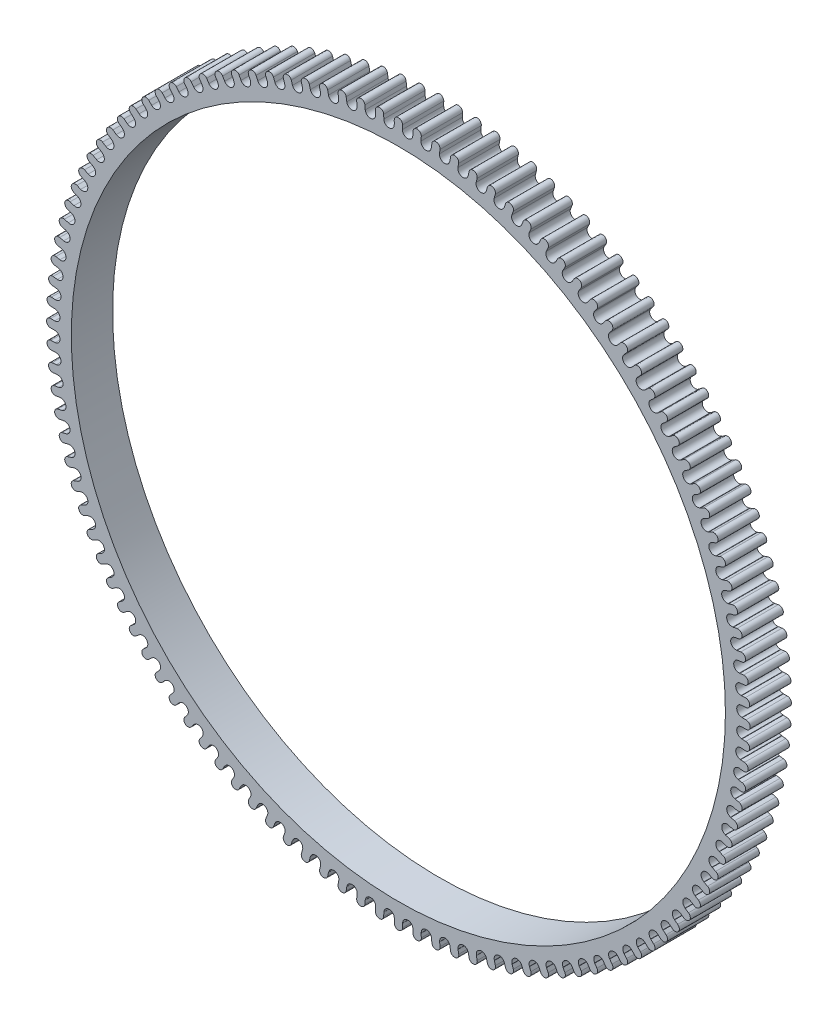
SolidWorks part; units mm, degrees
ref_plane "Front Plane" through (0, 0, 0) normal (0, 0, 1) x (1, 0, 0)
ref_plane "Top Plane" through (0, 0, 0) normal (0, 1, 0) x (1, 0, 0)
ref_plane "Right Plane" through (0, 0, 0) normal (1, 0, 0) x (0, 0, -1)
sketch "Sketch1" plane through (0, 0, 0) normal (0, 0, 1) x (1, 0, 0)
  circle A0 centre (0, 0) radius 79.25
  circle A1 centre (0, 0) radius 81.25
  dimension "D1" = 158.5
  dimension "D2" = 2
extrude "Boss-Extrude1" add sketch "Sketch1" along normal blind 10
sketch "Sketch2" plane through (0, 0, 10) normal (0, 0, 1) x (1, 0, 0)
  line L1 (1, 84.25) -> (0.9834, 83.25)
  line L2 (3.6329, 83.2298) -> (3.5431, 81.1727)
  line L3 (-1, 84.25) -> (-0.9643, 81.2443)
  line L4 (1, 84.25) -> (0.9997, 84.2263)
  circle A1 centre (0, 0) radius 81.25
  arc A2 (3.6329, 83.2298) -> (3.5207, 83.2346) centre (0, 0) ccw
  arc A3 (0.9997, 84.2263) -> (-0.9997, 84.2263) centre (0, 84.25) ccw
  arc A4 (0.9834, 83.25) -> (3.4808, 83.1535) centre (2.2334, 83.2362) ccw
  arc A5 (3.3969, 81.179) -> (-0.9643, 81.2443) centre (0, 0) ccw
  arc A6 (3.5207, 83.2346) -> (3.4808, 83.1535) centre (3.6286, 83.1311) ccw
  circle M1 centre (0, 0) radius 81.25
  dimension "D2" = 2
  dimension "D3" = 1
  dimension "D5" = 1.25
extrude "Boss-Extrude2" add sketch "Sketch2" against normal blind 10 contours A4 L1 A3 L4 L3 M1 region at (0.6417, 82.7918, 10)
pattern_circular "CirPattern1" count 116 every 3.104 about axis through (0, 0, 10) along (0, 0, 1) of "Boss-Extrude2"
